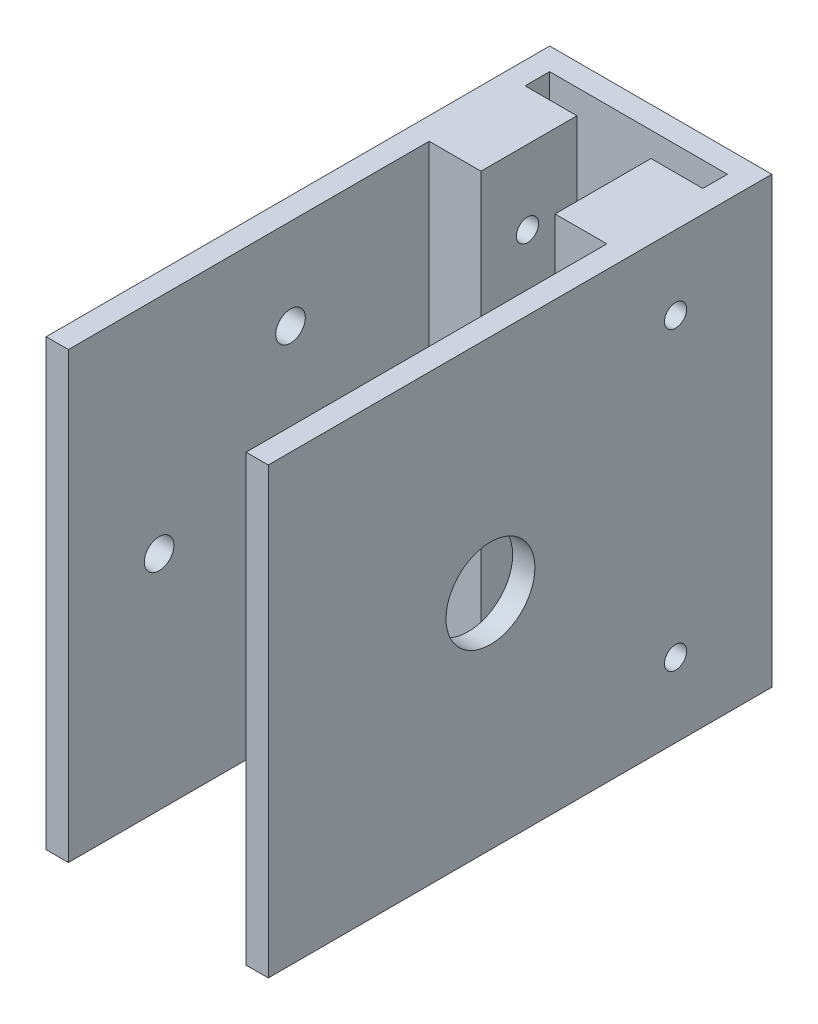
SolidWorks part; units mm, degrees
ref_plane "Front Plane" through (0, 0, 0) normal (0, 0, 1) x (1, 0, 0)
ref_plane "Top Plane" through (0, 0, 0) normal (0, 1, 0) x (1, 0, 0)
ref_plane "Right Plane" through (0, 0, 0) normal (1, 0, 0) x (0, 0, -1)
sketch "Sketch1" plane through (0, 0, 0) normal (0, 0, 1) x (1, 0, 0)
  line L0 (55, 0) -> (-55, 0) construction
  line L1 (-15, 30) -> (15, 30)
  line L2 (-15, 30) -> (-15, -30)
  line L3 (-15, -30) -> (15, -30)
  line L4 (15, 30) -> (15, -30)
  line L5 (-15, 30) -> (15, -30) construction
  line L6 (-15, -30) -> (15, 30) construction
  circle A0 centre (0, 15) radius 2.9
  circle A1 centre (0, -15) radius 2.9
  point P0 (0, 0)
  dimension "D3" = 15
  dimension "D4" = 5.8
  dimension "D1" = 30
  dimension "D2" = 60
extrude "Boss-Extrude1" add sketch "Sketch1" along normal blind 3
sketch "Sketch2" plane through (0, 0, 3) normal (0, 0, 1) x (1, 0, 0)
  line L0 (-15, -30) -> (15, -30) construction
  line L1 (-15, 30) -> (-12, 30)
  line L2 (-15, 30) -> (-15, -30)
  line L3 (-15, -30) -> (-12, -30)
  line L4 (-12, 30) -> (-12, -30)
  line L6 (15, 30) -> (12, 30)
  line L7 (15, 30) -> (15, -30)
  line L8 (15, -30) -> (12, -30)
  line L9 (12, 30) -> (12, -30)
  dimension "D1" = 3
  dimension "D2" = 3
extrude "Boss-Extrude2" add sketch "Sketch2" along normal blind 65
sketch "Sketch5" plane through (0, 30, 0) normal (0, 1, 0) x (1, 0, 0)
  line L0 (12, -68) -> (12, -3) construction
  line L2 (12, -6.3201) -> (5, -6.3201)
  line L3 (12, -6.3201) -> (12, -19.2778)
  line L4 (12, -19.2778) -> (5, -19.2778)
  line L5 (5, -6.3201) -> (5, -19.2778)
  line L6 (0, -33) -> (0, 33) construction
  line L7 (-12, -19.2778) -> (-5, -19.2778)
  line L8 (-12, -6.3201) -> (-5, -6.3201)
  line L9 (-5, -6.3201) -> (-5, -19.2778)
  line M5 (-12, -68) -> (-12, -3)
  line M7 (12, -3) -> (12, -68)
  dimension "D1" = 7
extrude "Boss-Extrude3" add sketch "Sketch5" against normal up to surface (60 mm away) contours L2 L5 L4 M7 | L9 L8 L7 M5 region at (8.5, 30, 12.799) region at (-8.5, 30, 12.799) up to face at (0, -30, 34.75)
sketch "Sketch3" plane through (-15, 0, 0) normal (-1, 0, 0) x (0, 0, 1)
  line L0 (68, 30) -> (0, 30) construction
  line L1 (0, 30) -> (0, -30) construction
  line L3 (16.5, 0) -> (-16.5, 0) construction
  circle A0 centre (13, 20) radius 1.5
  circle A1 centre (38, 0) radius 6
  circle A2 centre (20.25, 0) radius 2
  circle A4 centre (38, 17.75) radius 2
  circle A5 centre (55.75, 0) radius 2
  circle A6 centre (38, -17.75) radius 2
  circle A7 centre (13, -20) radius 1.5
  point P20 (38, 0)
  dimension "D1" = 3
  dimension "D2" = 10
  dimension "D3" = 13
  dimension "D4" = 12
  dimension "D5" = 4
  dimension "D6" = 17.75
  dimension "D7" = 38
extrude "Cut-Extrude1" cut sketch "Sketch3" against normal up to next
sketch "Sketch4" plane through (12, 0, 0) normal (-1, 0, 0) x (0, 0, 1)
  circle A0 centre (13, -20) radius 1.5 construction
  circle A1 centre (13, 20) radius 1.5 construction
  circle A2 centre (38, 0) radius 6 construction
  circle A3 centre (13, -20) radius 1.5
  circle A4 centre (13, 20) radius 1.5
  circle A5 centre (38, 0) radius 6
extrude "Cut-Extrude2" cut sketch "Sketch4" against normal through all both and the other way through all
